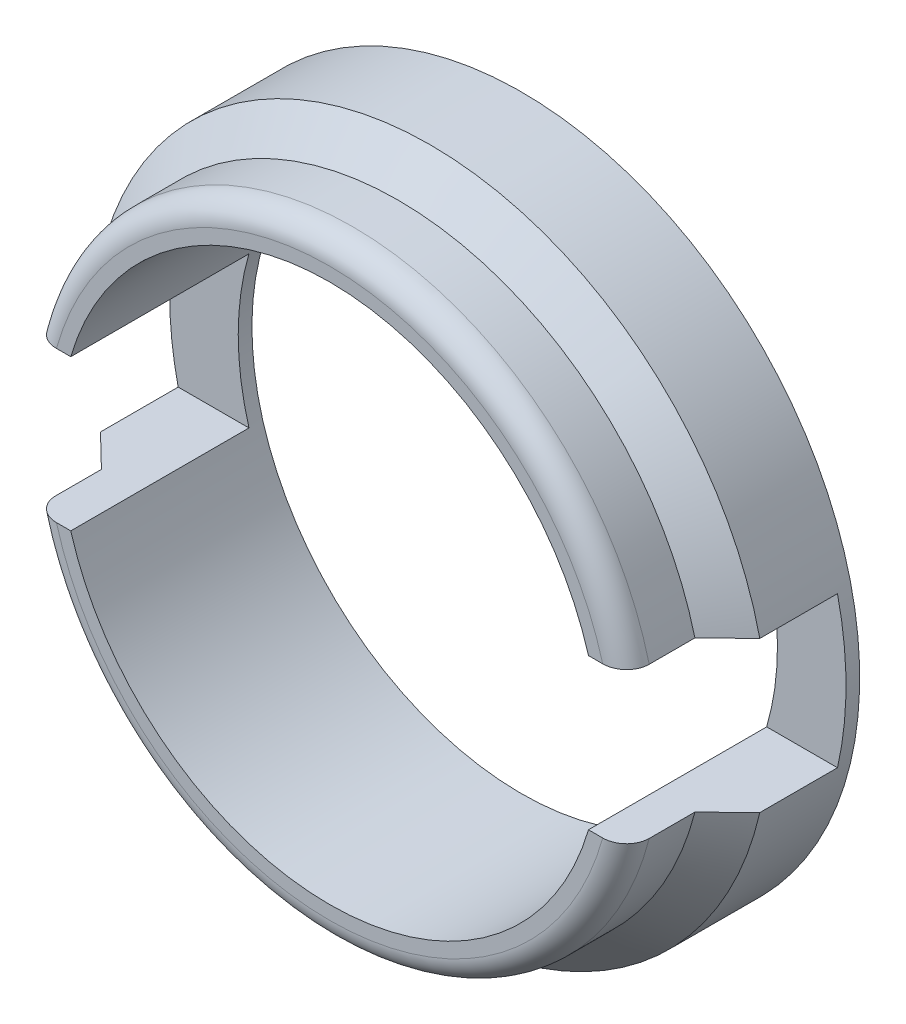
SolidWorks part; units mm, degrees
ref_plane "Alzado" through (0, 0, 0) normal (0, 0, 1) x (1, 0, 0)
ref_plane "Planta" through (0, 0, 0) normal (0, 1, 0) x (1, 0, 0)
ref_plane "Vista lateral" through (0, 0, 0) normal (1, 0, 0) x (0, 0, -1)
sketch "Croquis1" plane through (0, 0, 0) normal (0, 0, 1) x (1, 0, 0)
  circle A0 centre (0, 0) radius 5.9
  circle A1 centre (0, 0) radius 6.7
  dimension "D1" = 11.8
  dimension "D2" = 13.4
extrude "Saliente-Extruir1" add sketch "Croquis1" along normal blind 4.2
sketch "Croquis3" plane through (0, 0, 0) normal (0, 0, -1) x (-1, 0, 0)
  circle A0 centre (0, 0) radius 5.9
  circle A1 centre (0, 0) radius 7.4
  circle A2 centre (0, 0) radius 6.7 construction
  dimension "D1" = 0.7
extrude "Saliente-Extruir2" add sketch "Croquis3" against normal blind 2
fillet "Redondeo1" radius 0.5 1 edges at (6.7, 0, 4.2)
chamfer "Chaflán1" distance 0.7 angle 45 1 edges at (-6.7, 0, 2)
sketch "Croquis2" plane through (0, 0, 4.2) normal (0, 0, 1) x (1, 0, 0)
  line L1 (-10.2579, 1.65) -> (10.2579, 1.65)
  line L2 (-10.2579, 1.65) -> (-10.2579, -1.65)
  line L3 (-10.2579, -1.65) -> (10.2579, -1.65)
  line L4 (10.2579, 1.65) -> (10.2579, -1.65)
  line L5 (-10.2579, 1.65) -> (10.2579, -1.65) construction
  line L6 (-10.2579, -1.65) -> (10.2579, 1.65) construction
  point P0 (0, 0)
  dimension "D1" = 3.3
extrude "Cortar-Extruir1" cut sketch "Croquis2" against normal blind 3.9
